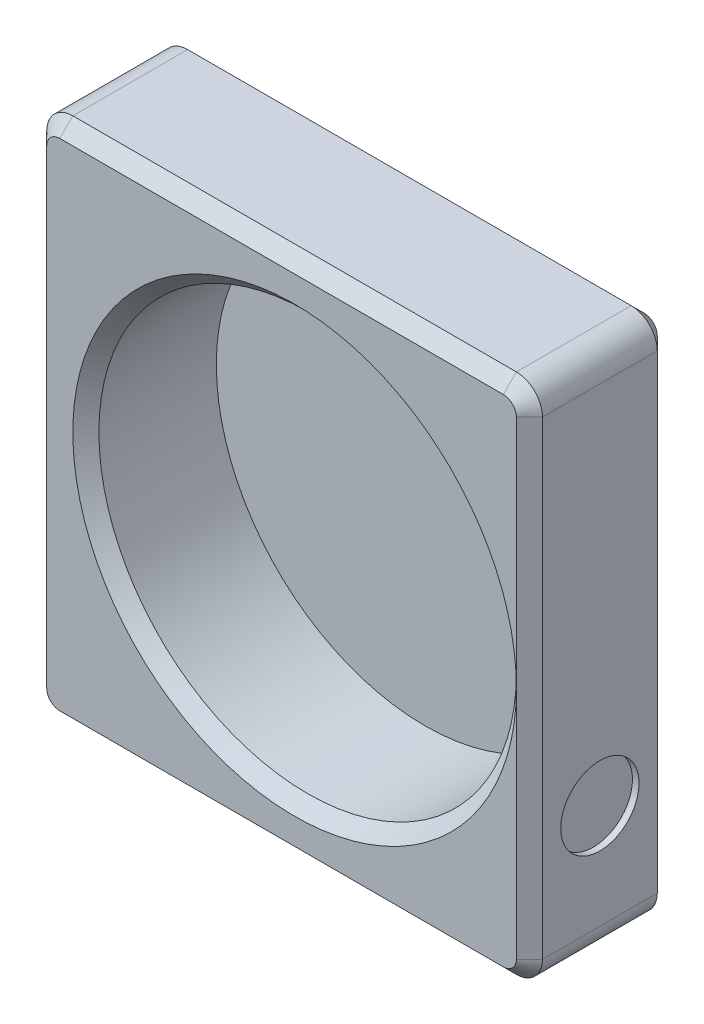
SolidWorks part; units mm, degrees
ref_plane "Front Plane" through (0, 0, 0) normal (0, 0, 1) x (1, 0, 0)
ref_plane "Top Plane" through (0, 0, 0) normal (0, 1, 0) x (1, 0, 0)
ref_plane "Right Plane" through (0, 0, 0) normal (1, 0, 0) x (0, 0, -1)
sketch "Sketch1" plane through (0, 0, 0) normal (0, 0, 1) x (1, 0, 0)
  line L1 (-10, -10) -> (10, -10)
  line L2 (-10, -10) -> (-10, 10)
  line L3 (-10, 10) -> (10, 10)
  line L4 (10, -10) -> (10, 10)
  line L5 (-10, -10) -> (10, 10) construction
  line L6 (-10, 10) -> (10, -10) construction
  point P0 (0, 0)
  dimension "D1" = 20
  dimension "D2" = 20
extrude "Boss-Extrude1" add sketch "Sketch1" along normal blind 5.4
sketch "Sketch2" plane through (0, 0, 5.4) normal (0, 0, 1) x (1, 0, 0)
  circle A0 centre (0, 0) radius 8
  dimension "D1" = 16
extrude "Cut-Extrude1" cut sketch "Sketch2" against normal blind 5
sketch "Sketch4" plane through (0, 0, 5.4) normal (0, 0, 1) x (1, 0, 0)
  line L0 (10, 10) -> (9, 10)
  line L1 (10, 10) -> (-10, 10) construction
  line L2 (9, 10) -> (9, -10)
  line L3 (-10, -10) -> (10, -10) construction
  line L4 (9, -10) -> (10, -10)
  line L5 (10, -10) -> (10, 10)
  dimension "D1" = 1
extrude "Cut-Extrude3" cut sketch "Sketch4" against normal blind 10
sketch "Sketch3" plane through (9, 0, 0) normal (1, 0, 0) x (0, 0, -1)
  line L0 (0, -5) -> (-5.4, -5) construction
  line L4 (-5.4, 10) -> (-5.4, -10) construction
  line L5 (0, -10) -> (0, 10) construction
  line L6 (0, -10) -> (-5.4, -10) construction
  circle A0 centre (-2.7, -5) radius 1.5
  point P3 (-5.4, 0)
  point P4 (0, 0)
  point P7 (0, 0)
  point P9 (0, 0)
  point P10 (0, 0)
  point P12 (-5.4, 5)
  point P15 (0, 5)
  dimension "D1" = 3
  dimension "D2" = 5
extrude "Cut-Extrude2" cut sketch "Sketch3" against normal blind 0.25
sketch "Sketch5" plane through (-10, 0, 0) normal (-1, 0, 0) x (0, 0, 1)
  line L0 (0, 5) -> (5.4, 5) construction
  line L1 (0, 10) -> (0, -10) construction
  line L2 (5.4, 10) -> (5.4, -10) construction
  line L3 (5.4, 10) -> (0, 10) construction
  line L4 (0, 4.5) -> (0, 5.5)
  line L5 (0, 5.5) -> (5.4, 5.5)
  line L6 (5.4, 5.5) -> (5.4, 4.5)
  line L7 (0, 4.5) -> (5.4, 4.5)
  dimension "D1" = 5
  dimension "D2" = 1
extrude "Cut-Extrude4" cut sketch "Sketch5" against normal blind 0.25
fillet "Fillet1" radius 1 4 edges at (-10, -10, 2.7) (-10, 10, 2.7) (9, -10, 2.7) (9, 10, 2.7)
chamfer "Chamfer1" distance 0.5 angle 45 25 edges at (-0.5, 10, 0) (-9.7071, 9.7071, 0) (-10, -2.25, 0) (-10, 7.25, 0) (-9.7071, -9.7071, 0) (-0.5, -10, 0) (-9.7071, -9.7071, 5.4) (-10, 7.25, 5.4) (-10, -2.25, 5.4) (-9.7071, 9.7071, 5.4) (-0.5, 10, 5.4) (-0.5, -10, 5.4) (8, 0, 5.4) (9, 0, 0) (-9.875, 5.5, 0) (-9.75, 5, 0) (-9.875, 4.5, 0) (-9.875, 4.5, 5.4) (-9.75, 5, 5.4) (-9.875, 5.5, 5.4) (9, 0, 5.4) (8.7071, 9.7071, 0) (8.7071, -9.7071, 0) (8.7071, 9.7071, 5.4) (8.7071, -9.7071, 5.4)
